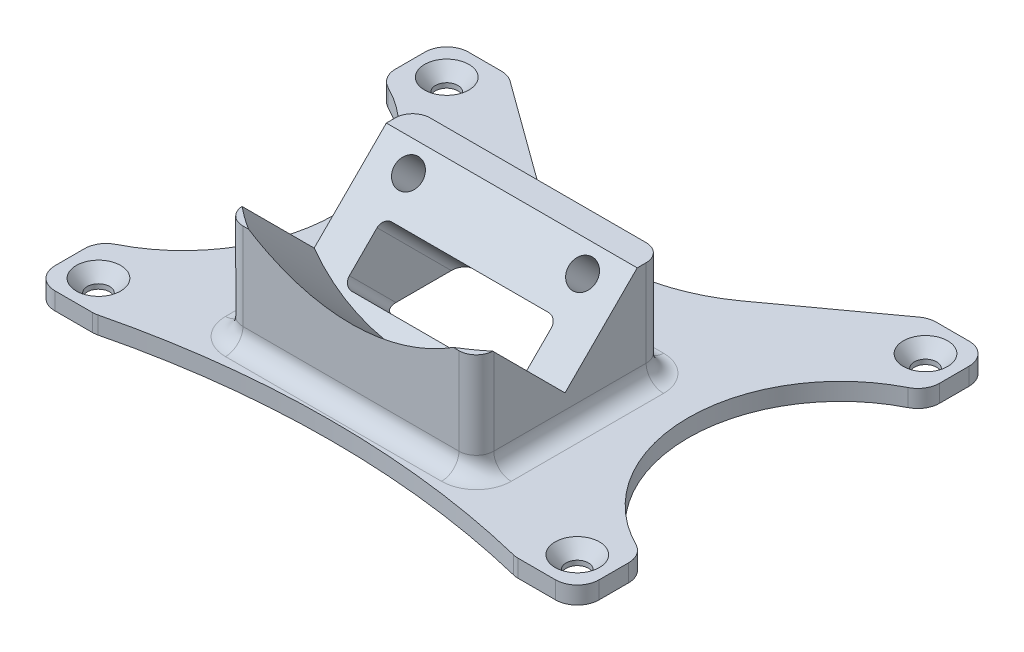
SolidWorks part; units mm, degrees
ref_plane "Front Plane" through (0, 0, 0) normal (0, 0, 1) x (1, 0, 0)
ref_plane "Top Plane" through (0, 0, 0) normal (0, 1, 0) x (1, 0, 0)
ref_plane "Right Plane" through (0, 0, 0) normal (1, 0, 0) x (0, 0, -1)
sketch "Sketch1" plane through (0, 0, 0) normal (0, 1, 0) x (1, 0, 0)
  line L0 (39.6875, -30.1625) -> (-39.6875, 30.1625) construction
  line L1 (-36.5125, 30.1625) -> (36.5125, 30.1625)
  line L2 (-39.6875, 26.9875) -> (-39.6875, -26.9875)
  line L3 (-36.5125, -30.1625) -> (36.5125, -30.1625)
  line L4 (39.6875, 26.9875) -> (39.6875, -26.9875)
  line L5 (34.925, 25.4) -> (-34.925, -25.4) construction
  line L6 (-34.925, 25.4) -> (34.925, 25.4) construction
  line L7 (-34.925, 25.4) -> (-34.925, -25.4) construction
  line L8 (-34.925, -25.4) -> (34.925, -25.4) construction
  line L9 (34.925, 25.4) -> (34.925, -25.4) construction
  arc A0 (-39.6875, -26.9875) -> (-36.5125, -30.1625) centre (-36.5125, -26.9875) ccw
  arc A1 (36.5125, -30.1625) -> (39.6875, -26.9875) centre (36.5125, -26.9875) ccw
  arc A2 (36.5125, 30.1625) -> (39.6875, 26.9875) centre (36.5125, 26.9875) cw
  arc A3 (-36.5125, 30.1625) -> (-39.6875, 26.9875) centre (-36.5125, 26.9875) ccw
  point P16 (39.6875, 30.1625)
  dimension "D5" = 3.175
  dimension "D1" = 79.375
  dimension "D2" = 69.85
  dimension "D3" = 50.8
  dimension "D4" = 60.325
extrude "Boss-Extrude1" add sketch "Sketch1" along normal blind 2.54
hole_wizard "CSK for #4 Flat Head Machine Screw1" positions "Sketch2" profile "Sketch3" countersink size "#4" standard "ANSI Inch" end condition up to next
sketch "Sketch2" plane through (0, 2.54, 0) normal (0, 1, 0) x (1, 0, 0)
  point P0 (-34.925, 25.4)
  point P3 (-34.925, -25.4)
  point P6 (34.925, -25.4)
  point P9 (34.925, 25.4)
sketch "Sketch3" plane through (-34.925, 2.54, -25.4) normal (1, 0, 0) x (0, 0, 1)
  line L0 (0, 0) -> (0, 2.54)
  line L1 (0, 2.54) -> (1.6319, 2.54)
  line L2 (1.6319, 2.54) -> (1.6319, 1.8481)
  line L3 (1.6319, 1.8481) -> (3.2385, 0)
  line L5 (3.2385, 0) -> (0, 0)
  line L6 (-1.6319, 1.8481) -> (-3.2385, 0) construction
  line L11 (0, -6.35) -> (0, 107.95) construction
  dimension "Thru Hole Dia." = 3.2639
  dimension "Thru Hole Depth" = 2.54
  dimension "Near C'Sink Dia." = 6.477
  dimension "Near C'Sink Angle" = 82
sketch "Sketch5" plane through (0, 2.54, 0) normal (0, 1, 0) x (1, 0, 0)
  line L0 (18.2975, 3.81) -> (-18.2975, -23.495) construction
  line L1 (-18.2975, 3.81) -> (18.2975, 3.81)
  line L2 (-18.2975, 3.81) -> (-18.2975, -23.495)
  line L3 (-18.2975, -23.495) -> (18.2975, -23.495)
  line L4 (18.2975, 3.81) -> (18.2975, -23.495)
  line L5 (0, -9.8425) -> (0, 0) construction
  line L6 (39.6875, -30.1625) -> (-39.6875, 30.1625) construction
  dimension "D1" = 36.5951
  dimension "D2" = 27.305
  dimension "D3" = 23.495
extrude "Boss-Extrude2" add sketch "Sketch5" along normal blind 15.24
sketch "Sketch4" plane through (0, 0, 0) normal (1, 0, 0) x (0, 0, -1)
  line L0 (-32.2443, 22.0525) -> (-6.188, 48.1087)
  line L1 (-32.2443, 22.0525) -> (-14.0018, 3.81)
  line L2 (-14.0018, 3.81) -> (12.0544, 29.8662)
  line L3 (12.0544, 29.8662) -> (-6.188, 48.1087)
  line L4 (26.9875, 0) -> (-26.9875, 0) construction
  line L5 (-23.495, 2.54) -> (3.81, 2.54) construction
  point P6 (2.9332, 38.9875)
  point P7 (-13.8222, 3.4018)
  point P12 (0, 0)
  dimension "D1" = 36.849
  dimension "D2" = 25.7988
  dimension "D3" = 45
  dimension "D4" = 1.27
  dimension "D5" = 12.0544
revolve "Cut-Revolve1" cut sketch "Sketch4" angle 360 about L3
sketch "Sketch8" plane through (0, 8.9059, 8.9059) normal (0, 0.7071, 0.7071) x (1, 0, 0)
  line L0 (12.7, 9.1957) -> (-12.7, 9.1957) construction
  line L1 (0, 9.1957) -> (0, 0) construction
  line L2 (34.925, 17.9605) -> (-34.925, -17.9605) construction
  circle A0 centre (-12.7, 9.1957) radius 2.0193
  circle A1 centre (12.7, 9.1957) radius 2.0193
  dimension "D1" = 4.0386
  dimension "D2" = 9.1957
  dimension "D3" = 25.4
extrude "Cut-Extrude2" cut sketch "Sketch8" against normal up to next
fillet "Fillet1" radius 2.54 8 edges at (0, 2.54, -3.81) (18.2975, 2.54, 9.8425) (0, 2.54, 23.495) (-18.2975, 2.54, 9.8425) (18.2975, 10.16, -3.81) (-18.2975, 10.16, -3.81) (18.2975, 10.16, 23.495) (-18.2975, 10.16, 23.495)
sketch "Sketch9" plane through (0, 2.54, 0) normal (0, 1, 0) x (1, 0, 0)
  line L1 (-30.6773, 30.1625) -> (30.6773, 30.1625)
  line L4 (0, 30.1625) -> (0, 0) construction
  line L5 (-39.6875, 20.6375) -> (-39.6875, -20.6375)
  line L6 (14.9396, 18.7169) -> (30.6773, 30.1625)
  line L7 (-36.5125, 30.1625) -> (36.5125, 30.1625) construction
  line L8 (-39.6875, 26.9875) -> (-39.6875, -26.9875) construction
  line L9 (34.925, 25.4) -> (-34.925, -25.4) construction
  line L10 (-14.9396, 18.7169) -> (-30.6773, 30.1625)
  line L11 (-39.6875, 0) -> (0, 0) construction
  line L15 (39.6875, 20.6375) -> (39.6875, -20.6375)
  line L16 (-30.6773, -30.1625) -> (30.6773, -30.1625)
  line L17 (-36.5125, -30.1625) -> (36.5125, -30.1625) construction
  line L18 (0, -30.1625) -> (0, 0) construction
  line L19 (0, 7.8518) -> (-14.9396, 18.7169) construction
  line L20 (0, 7.8518) -> (14.9396, 18.7169) construction
  line L21 (-14.9396, 18.7169) -> (14.9396, 18.7169) construction
  arc A0 (-39.6875, -20.6375) -> (-39.6875, 20.6375) centre (-47.9364, 0) ccw
  arc A1 (39.6875, -20.6375) -> (39.6875, 20.6375) centre (47.9364, 0) cw
  arc A2 (30.6773, -30.1625) -> (-30.6773, -30.1625) centre (0, -153.4017) ccw
  arc A3 (-14.9396, 18.7169) -> (14.9396, 18.7169) centre (0, 39.2588) ccw
  dimension "D3" = 44.45
  dimension "D4" = 127
  dimension "D5" = 25.4
  dimension "D1" = 6.35
  dimension "D2" = 41.275
extrude "Cut-Extrude4" cut sketch "Sketch9" against normal blind 3.429
fillet "Fillet2" radius 3.175 8 edges at (-30.6773, 1.27, 30.1625) (-39.6875, 1.27, 20.6375) (-39.6875, 1.27, -20.6375) (-30.6773, 1.27, -30.1625) (30.6773, 1.27, -30.1625) (39.6875, 1.27, -20.6375) (39.6875, 1.27, 20.6375) (30.6773, 1.27, 30.1625)
sketch "Sketch10" plane through (0, 8.9059, 8.9059) normal (0, 0.7071, 0.7071) x (1, 0, 0)
  line L0 (12.7, 3.9896) -> (-12.7, -4.2654) construction
  line L1 (-12.7, 3.9896) -> (12.7, 3.9896)
  line L2 (-12.7, 3.9896) -> (-12.7, -4.2654)
  line L3 (-12.7, -4.2654) -> (12.7, -4.2654)
  line L4 (12.7, 3.9896) -> (12.7, -4.2654)
  line L5 (0, -0.1379) -> (0, 0) construction
  line L6 (39.6875, -21.3281) -> (-39.6875, 21.3281) construction
  point P8 (5.6468, -0.6674)
  arc M10 (-18.2975, -2.3428) -> (18.2975, -2.3428) centre (0, 29.6424) ccw
  dimension "D1" = 8.255
  dimension "D2" = 25.4
  dimension "D3" = 0.1379
extrude "Cut-Extrude5" cut sketch "Sketch10" against normal through all contours L4 L1 L2 L3 M10 region at (0, 8.8084, 9.0034)
fillet "Fillet3" radius 1.27 4 edges at (12.7, 5.8635, 0.2213) (-12.7, 5.8635, 0.2213) (-12.7, 2.9449, 8.9771) (12.7, 2.9449, 8.9771)
